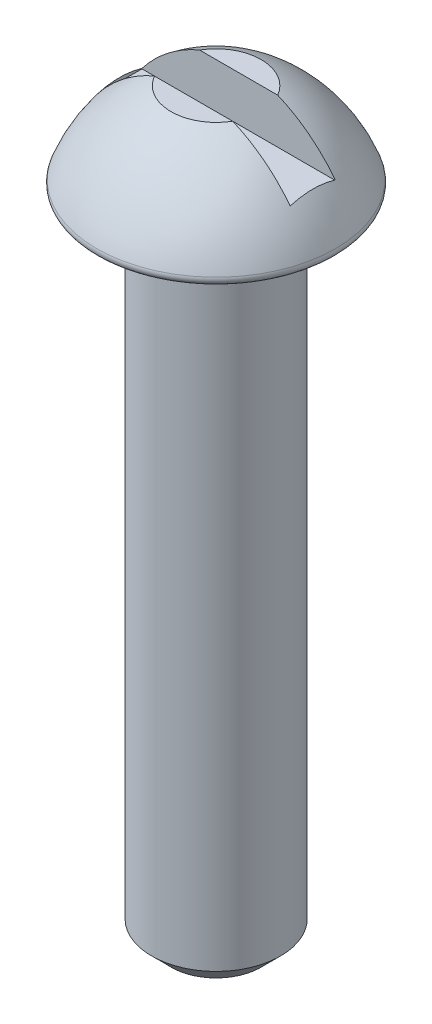
SolidWorks part; units mm, degrees
ref_plane "Спереди" through (0, 0, 0) normal (0, 0, 1) x (1, 0, 0)
ref_plane "Сверху" through (0, 0, 0) normal (0, 1, 0) x (1, 0, 0)
ref_plane "Справа" through (0, 0, 0) normal (1, 0, 0) x (0, 0, -1)
sketch "Эскиз1" plane through (0, 0, 0) normal (0, 0, 1) x (1, 0, 0)
  line L0 (1.9, 10.1) -> (1, 10.1)
  line L1 (0, 0) -> (0, 11.5)
  line L2 (1, 10.1) -> (1, 0.3)
  line L3 (1, 0.3) -> (0.7, 0)
  line L4 (0.7, 0) -> (0, 0)
  line L5 (0, 11.5) -> (0.7, 11.5)
  arc A0 (0.7, 11.5) -> (1.9, 10.1) centre (-0.307, 9.4226) cw
  dimension "D2" = 0.7
  dimension "D8" = 2.1
  dimension "D1" = 11.5
  dimension "D3" = 1
  dimension "D4" = 0.7
  dimension "D5" = 1.4
  dimension "D6" = 1.9
  dimension "D7" = 45
revolve "Повернуть1" add sketch "Эскиз1" angle 360 about L1
fillet "Скругление1" radius 0.1 1 edges at (0, 10.1, -1.9)
ref_axis "Ось1" through (0, -104.1565, 0) along (0, 1, 0)
sketch "Эскиз2" plane through (0, 11.5, 0) normal (0, 1, 0) x (-1, 0, 0)
  line L1 (1.5, -0.35) -> (-1.5, -0.35)
  line L2 (1.5, -0.35) -> (1.5, 0.35)
  line L3 (1.5, 0.35) -> (-1.5, 0.35)
  line L4 (-1.5, -0.35) -> (-1.5, 0.35)
  dimension "D1" = 0.7
  dimension "D2" = 0.35
  dimension "D3" = 3
  dimension "D4" = 1.5
extrude "Вырез-Вытянуть1" cut sketch "Эскиз2" against normal blind 0.7
